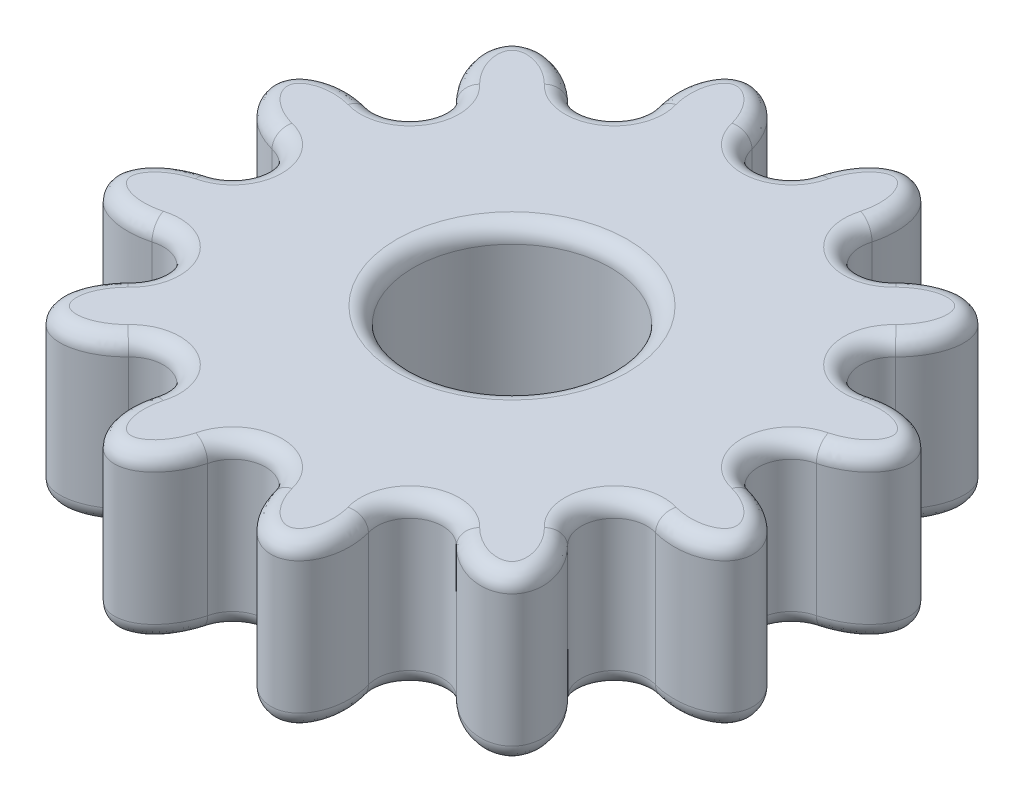
SolidWorks part; units mm, degrees
ref_plane "Front Plane" through (0, 0, 0) normal (0, 0, 1) x (1, 0, 0)
ref_plane "Top Plane" through (0, 0, 0) normal (0, 1, 0) x (1, 0, 0)
ref_plane "Right Plane" through (0, 0, 0) normal (1, 0, 0) x (0, 0, -1)
sketch "Sketch2" plane through (0, 0, 0) normal (0, 1, 0) x (1, 0, 0)
  line L0 (0, 16.9523) -> (0, 0) construction
  line L1 (1.9525, 16.519) -> (6.5686, 15.2821) construction
  line L2 (0, 34.6933) -> (0, -34.6933) construction
  line L3 (-45.7254, 0) -> (45.7254, 0) construction
  arc A2 (-1.9525, 16.519) -> (1.9525, 16.519) centre (0, 16.9523) ccw
  arc A4 (6.5686, 15.2821) -> (9.9504, 13.3296) centre (8.4762, 14.6812) ccw
  arc A6 (13.3296, 9.9504) -> (15.2821, 6.5686) centre (14.6812, 8.4762) ccw
  arc A8 (16.519, 1.9525) -> (16.519, -1.9525) centre (16.9523, 0) ccw
  arc A10 (15.2821, -6.5686) -> (13.3296, -9.9504) centre (14.6812, -8.4762) ccw
  arc A12 (9.9504, -13.3296) -> (6.5686, -15.2821) centre (8.4762, -14.6812) ccw
  arc A14 (1.9525, -16.519) -> (-1.9525, -16.519) centre (0, -16.9523) ccw
  arc A16 (-6.5686, -15.2821) -> (-9.9504, -13.3296) centre (-8.4762, -14.6812) ccw
  arc A18 (-13.3296, -9.9504) -> (-15.2821, -6.5686) centre (-14.6812, -8.4762) ccw
  arc A20 (-16.519, -1.9525) -> (-16.519, 1.9525) centre (-16.9523, 0) ccw
  arc A22 (-15.2821, 6.5686) -> (-13.3296, 9.9504) centre (-14.6812, 8.4762) ccw
  arc A24 (-9.9504, 13.3296) -> (-6.5686, 15.2821) centre (-8.4762, 14.6812) ccw
  ellipse E0 centre (4.2605, 15.9005) end of major axis (5.1764, 19.3185) minor radius 2.3895 (6.5686, 15.2821) -> (1.9525, 16.519) ccw
  ellipse E1 centre (11.64, 11.64) end of major axis (14.1421, 14.1421) minor radius 2.3895 (13.3296, 9.9504) -> (9.9504, 13.3296) ccw
  ellipse E2 centre (15.9005, 4.2605) end of major axis (19.3185, 5.1764) minor radius 2.3895 (16.519, 1.9525) -> (15.2821, 6.5686) ccw
  ellipse E3 centre (15.9005, -4.2605) end of major axis (19.3185, -5.1764) minor radius 2.3895 (15.2821, -6.5686) -> (16.519, -1.9525) ccw
  ellipse E4 centre (11.64, -11.64) end of major axis (9.1378, -9.1378) minor radius 2.3895 (9.9504, -13.3296) -> (13.3296, -9.9504) ccw
  ellipse E5 centre (4.2605, -15.9005) end of major axis (5.1764, -19.3185) minor radius 2.3895 (1.9525, -16.519) -> (6.5686, -15.2821) ccw
  ellipse E6 centre (-4.2605, -15.9005) end of major axis (-5.1764, -19.3185) minor radius 2.3895 (-6.5686, -15.2821) -> (-1.9525, -16.519) ccw
  ellipse E7 centre (-11.64, -11.64) end of major axis (-9.1378, -9.1378) minor radius 2.3895 (-13.3296, -9.9504) -> (-9.9504, -13.3296) ccw
  ellipse E8 centre (-15.9005, -4.2605) end of major axis (-12.4825, -3.3447) minor radius 2.3895 (-16.519, -1.9525) -> (-15.2821, -6.5686) ccw
  ellipse E9 centre (-15.9005, 4.2605) end of major axis (-19.3185, 5.1764) minor radius 2.3895 (-15.2821, 6.5686) -> (-16.519, 1.9525) ccw
  ellipse E10 centre (-11.64, 11.64) end of major axis (-9.1378, 9.1378) minor radius 2.3895 (-9.9504, 13.3296) -> (-13.3296, 9.9504) ccw
  ellipse E11 centre (-4.2605, 15.9005) end of major axis (-5.1764, 19.3185) minor radius 2.3895 (-1.9525, 16.519) -> (-6.5686, 15.2821) ccw
  point P3 (0, 0)
  point P15 (0, 0)
  point P16 (-5.1764, 19.3185)
  point P17 (-5.1764, 19.3185)
  point P18 (-4.2605, 16.0856)
  point P22 (-4.2605, 15.9005)
  point P27 (0, 0)
  point P150 (0, 0)
  dimension "D2" = 4
  dimension "D4" = 7.0772
  dimension "D8" = 3.905
  dimension "D3" = 20
  dimension "D5" = 69.3865
  dimension "D6" = 91.4509
  dimension "D7" = 4.7789
  dimension "D11" = 12
extrude "Boss-Extrude2" add sketch "Sketch2" along normal mid plane 10
sketch "Sketch4" plane through (0, 5, 0) normal (0, 1, 0) x (1, 0, 0)
  circle A0 centre (0, 0) radius 6
  dimension "D1" = 12
extrude "Cut-Extrude3" cut sketch "Sketch4" against normal blind 10
fillet "Fillet1" radius 1 50 edges at (0, -5, 6) (0, 5, 6) (0, -5, -14.9523) (-5.1764, -5, -19.3185) (-7.4762, -5, -12.9491) (-14.1421, -5, -14.1421) (-12.9491, -5, -7.4762) (-19.3185, -5, -5.1764) (-14.9523, -5, 0) (-19.3185, -5, 5.1764) (-12.9491, -5, 7.4762) (-14.1421, -5, 14.1421) (-7.4762, -5, 12.9491) (-5.1764, -5, 19.3185) (0, -5, 14.9523) (5.1764, -5, 19.3185) (7.4762, -5, 12.9491) (14.1421, -5, 14.1421) (12.9491, -5, 7.4762) (19.3185, -5, 5.1764) (14.9523, -5, 0) (19.3185, -5, -5.1764) (12.9491, -5, -7.4762) (14.1421, -5, -14.1421) (7.4762, -5, -12.9491) (5.1764, -5, -19.3185) (7.4762, 5, -12.9491) (14.1421, 5, -14.1421) (12.9491, 5, -7.4762) (19.3185, 5, -5.1764) (14.9523, 5, 0) (19.3185, 5, 5.1764) (12.9491, 5, 7.4762) (14.1421, 5, 14.1421) (7.4762, 5, 12.9491) (5.1764, 5, 19.3185) (0, 5, 14.9523) (-5.1764, 5, 19.3185) (-7.4762, 5, 12.9491) (-14.1421, 5, 14.1421) (-12.9491, 5, 7.4762) (-19.3185, 5, 5.1764) (-14.9523, 5, 0) (-19.3185, 5, -5.1764) (-12.9491, 5, -7.4762) (-14.1421, 5, -14.1421) (-7.4762, 5, -12.9491) (-5.1764, 5, -19.3185) (0, 5, -14.9523) (5.1764, 5, -19.3185)
